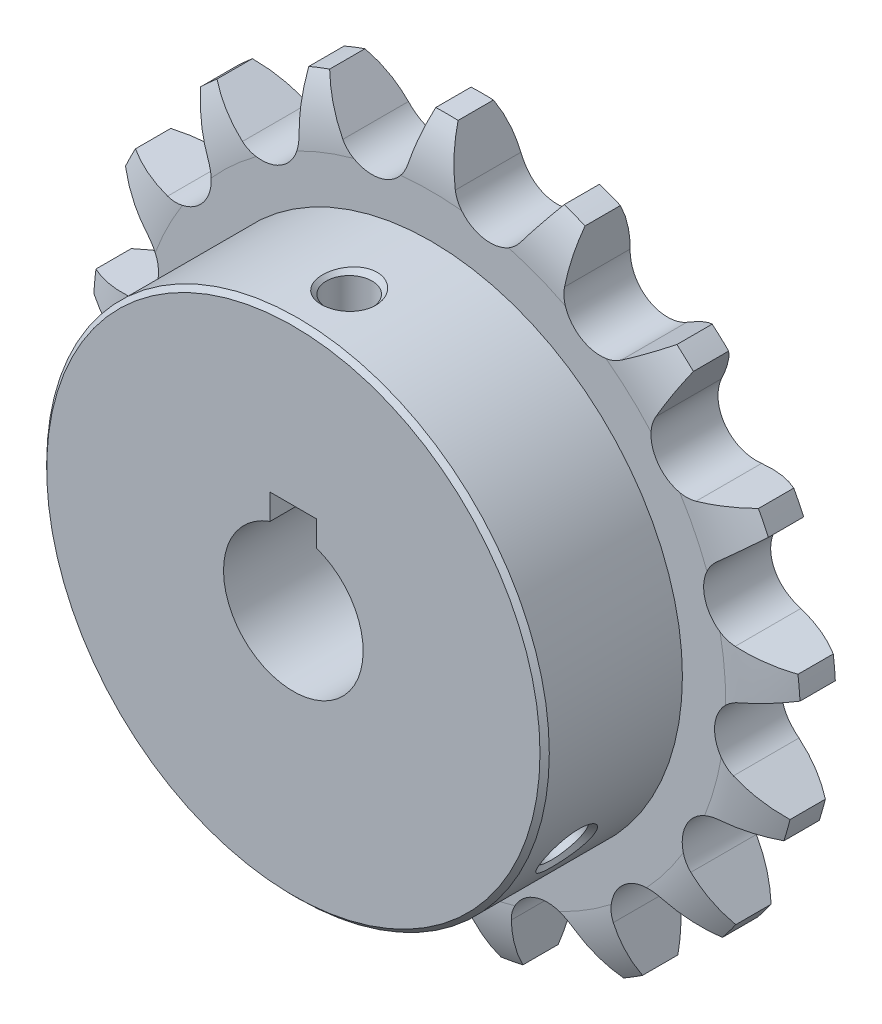
SolidWorks part; units mm, degrees
ref_plane "Front Plane" through (0, 0, 0) normal (0, 0, 1) x (1, 0, 0)
ref_plane "Top Plane" through (0, 0, 0) normal (0, 1, 0) x (1, 0, 0)
ref_plane "Right Plane" through (0, 0, 0) normal (1, 0, 0) x (0, 0, -1)
ref_plane "Plane1" through (0, 0, 0) normal (1, 0, 0) x (0, 0, -1)
sketch "Sketch1" plane through (0, 0, 0) normal (1, 0, 0) x (0, 0, -1)
  line L0 (-22, 7.5) -> (0, 7.5)
  line L1 (0, 7.5) -> (0, 31.6496)
  line L2 (-1.7016, 38) -> (-5.4984, 38)
  line L3 (-7.2, 31.6496) -> (-7.2, 27)
  line L4 (-7.2, 27) -> (-21.5, 27)
  line L5 (-21.5, 27) -> (-22, 26.5)
  line L6 (-22, 26.5) -> (-22, 7.5)
  line L7 (0, 0) -> (-3.6, 0) construction
  arc A0 (0, 31.6496) -> (-1.7016, 38) centre (-12.7008, 31.6496) ccw
  arc A1 (-5.4984, 38) -> (-7.2, 31.6496) centre (5.5008, 31.6496) ccw
revolve "Revolve1" add sketch "Sketch1" angle 360 about L7 reverse direction yes
ref_plane "Plane2" through (0, 0, 0) normal (0, 0, 1) x (1, 0, 0)
sketch "Sketch2" plane through (0, 0, 0) normal (0, 0, 1) x (1, 0, 0)
  line L0 (-37.9482, 2.3161) -> (-33.0556, 0.5314)
  line L1 (-32.3951, -6.5963) -> (-36.8765, -9.2496)
  line L2 (-36.8765, -9.2496) -> (-36.2223, -11.5488)
  line L3 (-36.2223, -11.5488) -> (-31.0154, -11.4455)
  line L4 (-27.8246, -17.8533) -> (-31.0449, -21.9463)
  line L5 (-31.0449, -21.9463) -> (-29.6044, -23.8539)
  line L6 (-29.6044, -23.8539) -> (-24.7864, -21.8766)
  line L7 (-19.4963, -26.6992) -> (-21.0206, -31.6791)
  line L8 (-21.0206, -31.6791) -> (-18.9882, -32.9374)
  line L9 (-18.9882, -32.9374) -> (-15.2098, -29.3532)
  line L10 (-8.5349, -31.9391) -> (-8.1573, -37.1334)
  line L11 (-8.1573, -37.1334) -> (-5.8076, -37.5726)
  line L12 (-5.8076, -37.5726) -> (-3.5791, -32.8655)
  line L13 (3.5791, -32.8655) -> (5.8076, -37.5726)
  line L14 (5.8076, -37.5726) -> (8.1573, -37.1334)
  line L15 (8.1573, -37.1334) -> (8.5349, -31.9391)
  line L16 (15.2098, -29.3532) -> (18.9882, -32.9374)
  line L17 (18.9882, -32.9374) -> (21.0206, -31.6791)
  line L18 (21.0206, -31.6791) -> (19.4963, -26.6992)
  line L19 (24.7864, -21.8766) -> (29.6044, -23.8539)
  line L20 (29.6044, -23.8539) -> (31.0449, -21.9463)
  line L21 (31.0449, -21.9463) -> (27.8246, -17.8533)
  line L22 (31.0154, -11.4455) -> (36.2223, -11.5488)
  line L23 (36.2223, -11.5488) -> (36.8765, -9.2496)
  line L24 (36.8765, -9.2496) -> (32.3951, -6.5963)
  line L25 (33.0556, 0.5314) -> (37.9482, 2.3161)
  line L26 (37.9482, 2.3161) -> (37.7276, 4.6963)
  line L27 (37.7276, 4.6963) -> (32.5904, 5.5516)
  line L28 (30.6314, 12.4366) -> (34.5489, 15.8682)
  line L29 (34.5489, 15.8682) -> (33.4835, 18.0079)
  line L30 (33.4835, 18.0079) -> (28.3842, 16.9497)
  line L31 (24.0703, 22.6621) -> (26.4837, 27.2771)
  line L32 (26.4837, 27.2771) -> (24.7172, 28.8875)
  line L33 (24.7172, 28.8875) -> (20.3445, 26.0586)
  line L34 (14.2584, 29.827) -> (14.8417, 35.0022)
  line L35 (14.8417, 35.0022) -> (12.6127, 35.8657)
  line L36 (12.6127, 35.8657) -> (9.5572, 31.6482)
  line L37 (2.5208, 32.9636) -> (1.1952, 38)
  line L38 (1.1952, 38) -> (-1.1952, 38)
  line L39 (-1.1952, 38) -> (-2.5208, 32.9636)
  line L40 (-9.5572, 31.6482) -> (-12.6127, 35.8657)
  line L41 (-12.6127, 35.8657) -> (-14.8417, 35.0022)
  line L42 (-14.8417, 35.0022) -> (-14.2584, 29.827)
  line L43 (-20.3445, 26.0586) -> (-24.7172, 28.8875)
  line L44 (-24.7172, 28.8875) -> (-26.4837, 27.2771)
  line L45 (-26.4837, 27.2771) -> (-24.0703, 22.6621)
  line L46 (-28.3842, 16.9497) -> (-33.4835, 18.0079)
  line L47 (-33.4835, 18.0079) -> (-34.5489, 15.8682)
  line L48 (-34.5489, 15.8682) -> (-30.6314, 12.4366)
  line L49 (-32.5904, 5.5516) -> (-37.7276, 4.6963)
  line L50 (-37.7276, 4.6963) -> (-37.9482, 2.3161)
  circle A0 centre (0, 0) radius 69.12
  arc A1 (-33.0556, 0.5314) -> (-32.3951, -6.5963) centre (-34.4126, -3.1888) cw
  arc A2 (-31.0154, -11.4455) -> (-27.8246, -17.8533) centre (-30.9368, -15.4047) cw
  arc A3 (-24.7864, -21.8766) -> (-19.4963, -26.6992) centre (-23.2829, -25.5401) cw
  arc A4 (-15.2098, -29.3532) -> (-8.5349, -31.9391) centre (-12.4845, -32.2262) cw
  arc A5 (-3.5791, -32.8655) -> (3.5791, -32.8655) centre (0, -34.56) cw
  arc A6 (8.5349, -31.9391) -> (15.2098, -29.3532) centre (12.4845, -32.2262) cw
  arc A7 (19.4963, -26.6992) -> (24.7864, -21.8766) centre (23.2829, -25.5401) cw
  arc A8 (27.8246, -17.8533) -> (31.0154, -11.4455) centre (30.9368, -15.4047) cw
  arc A9 (32.3951, -6.5963) -> (33.0556, 0.5314) centre (34.4126, -3.1888) cw
  arc A10 (32.5904, 5.5516) -> (30.6314, 12.4366) centre (33.2407, 9.4578) cw
  arc A11 (28.3842, 16.9497) -> (24.0703, 22.6621) centre (27.5795, 20.8271) cw
  arc A12 (20.3445, 26.0586) -> (14.2584, 29.827) centre (18.1935, 29.3835) cw
  arc A13 (9.5572, 31.6482) -> (2.5208, 32.9636) centre (6.3504, 33.9716) cw
  arc A14 (-2.5208, 32.9636) -> (-9.5572, 31.6482) centre (-6.3504, 33.9716) cw
  arc A15 (-14.2584, 29.827) -> (-20.3445, 26.0586) centre (-18.1935, 29.3835) cw
  arc A16 (-24.0703, 22.6621) -> (-28.3842, 16.9497) centre (-27.5795, 20.8271) cw
  arc A17 (-30.6314, 12.4366) -> (-32.5904, 5.5516) centre (-33.2407, 9.4578) cw
extrude "Cut-Extrude1" cut sketch "Sketch2" along normal blind 7.2
ref_plane "Plane3" through (0, 0, 16) normal (0, 0, 1) x (1, 0, 0)
sketch "Sketch3" plane through (0, 0, 16) normal (0, 0, 1) x (1, 0, 0)
  line L0 (0, 27) -> (3, 27)
  line L1 (3, 27) -> (2.4585, 26.4585)
  line L2 (2.4585, 26.4585) -> (2.4585, 0)
  line L3 (2.4585, 0) -> (0, 0)
  line L4 (0, 0) -> (0, 27)
  line L5 (0, 0) -> (0, 27) construction
revolve "Cut-Revolve1" cut sketch "Sketch3" angle 360 about L5 reverse direction yes
cosmetic thread "Cosmetic Thread1" parameters "D1"=17.2, "D2"=6
ref_plane "Plane4" through (0, 0, 16) normal (0, 0, 1) x (1, 0, 0)
sketch "Sketch4" plane through (0, 0, 16) normal (0, 0, 1) x (1, 0, 0)
  line L0 (23.3827, -13.5) -> (21.8827, -16.0981)
  line L1 (21.8827, -16.0981) -> (21.6845, -15.3584)
  line L2 (21.6845, -15.3584) -> (-1.2293, -2.1291)
  line L3 (-1.2293, -2.1291) -> (0, 0)
  line L4 (0, 0) -> (23.3827, -13.5)
  line L5 (0, 0) -> (23.3827, -13.5) construction
revolve "Cut-Revolve2" cut sketch "Sketch4" angle 360 about L5 reverse direction yes
cosmetic thread "Cosmetic Thread2" parameters "D1"=19.5, "D2"=6
ref_plane "Plane5" through (0, 0, 0) normal (0, 0, 1) x (1, 0, 0)
sketch "Sketch5" plane through (0, 0, 0) normal (0, 0, 1) x (1, 0, 0)
  line L0 (-2.5, 9.8) -> (-2.5, 0)
  line L1 (-2.5, 0) -> (2.5, 0)
  line L2 (2.5, 0) -> (2.5, 9.8)
  line L3 (2.5, 9.8) -> (-2.5, 9.8)
extrude "Cut-Extrude2" cut sketch "Sketch5" along normal blind 22
